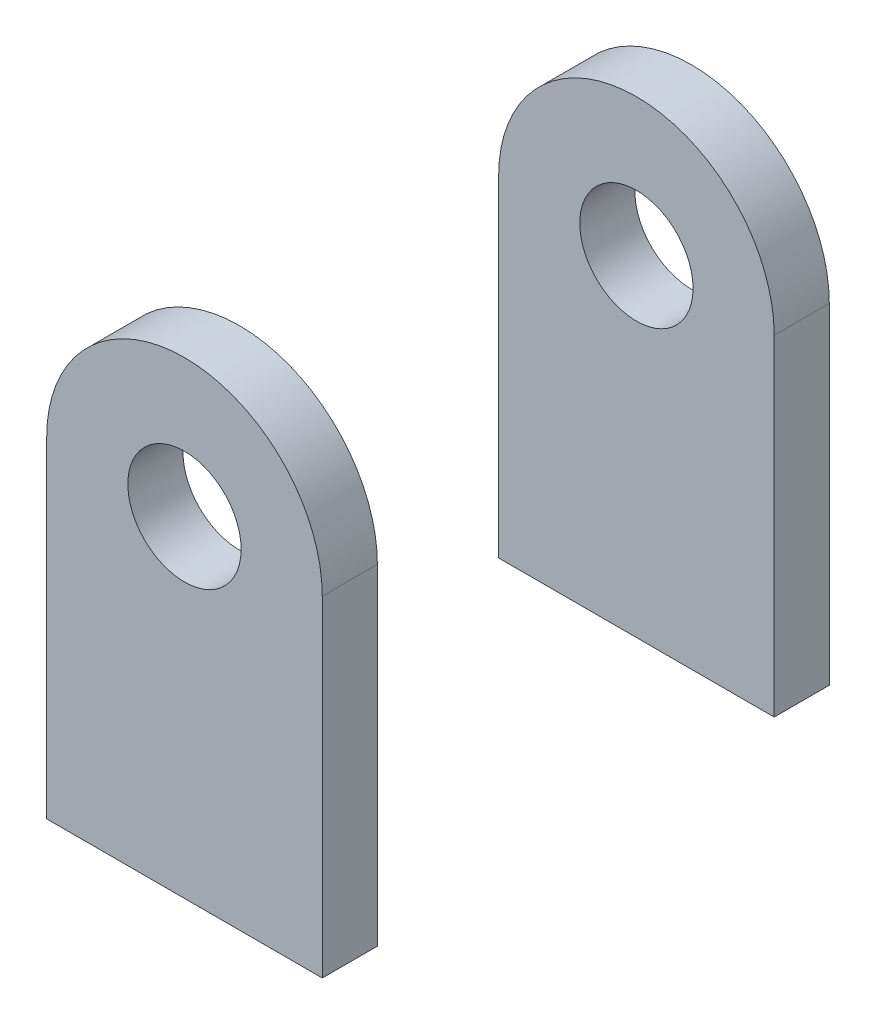
SolidWorks part; units mm, degrees
material "AISI 4130 Steel, normalized at 870C"
ref_plane "Front Plane" through (0, 0, 0) normal (0, 0, 1) x (1, 0, 0)
ref_plane "Top Plane" through (0, 0, 0) normal (0, 1, 0) x (1, 0, 0)
ref_plane "Right Plane" through (0, 0, 0) normal (1, 0, 0) x (0, 0, -1)
sketch "Sketch1" plane through (0, 0, 0) normal (0, 0, 1) x (1, 0, 0)
  line L0 (7.9375, 0) -> (7.9375, -19.05)
  line L1 (7.9375, -19.05) -> (-7.9375, -19.05)
  line L2 (-7.9375, -19.05) -> (-7.9375, 0)
  line L3 (0, 0) -> (0, -19.05) construction
  circle A0 centre (0, 0) radius 3.2639
  circle A1 centre (0, 0) radius 7.9375
  dimension "D1" = 6.5278
  dimension "D2" = 15.875
  dimension "D3" = 19.05
extrude "Boss-Extrude1" add sketch "Sketch1" along normal blind 3.175 from offset 11.43 contours A1 A0 | A1 L2 L1 L0 | L3 A1 L2 L1 region at (5.4539, -5.4539, 0) region at (4.2606, -12.5196, 0) region at (-4.2606, -12.5196, 0)
extrude "Boss-Extrude2" add sketch "Sketch1<4>" against normal blind 3.175 from offset 11.43 separate body contours A1 A0 | A1 L2 L1 L0 | L3 A1 L2 L1 region at (5.4539, -5.4539, 0) region at (4.2606, -12.5196, 0) region at (-4.2606, -12.5196, 0) offset against normal yes
sketch "Sketch1<4>" plane through (0, 0, 0) normal (0, 0, 1) x (1, 0, 0) same geometry as "Sketch1"
equation "\"Width Between Tabs\" = .9"
equation "\"Tab Thickness\"= 1 / 8"
equation "\"D19@Boss-Extrude1\"=\"Width Between Tabs\"/2"
equation "\"D1@Boss-Extrude1\"=\"Tab Thickness\""
equation "\"D19@Boss-Extrude2\"=\"Width Between Tabs\"/2"
equation "\"D1@Boss-Extrude2\"=\"Tab Thickness\""
equation "\"Hole Diameter\"= .257"
equation "\"D1@Sketch1\"=\"Hole Diameter\""
